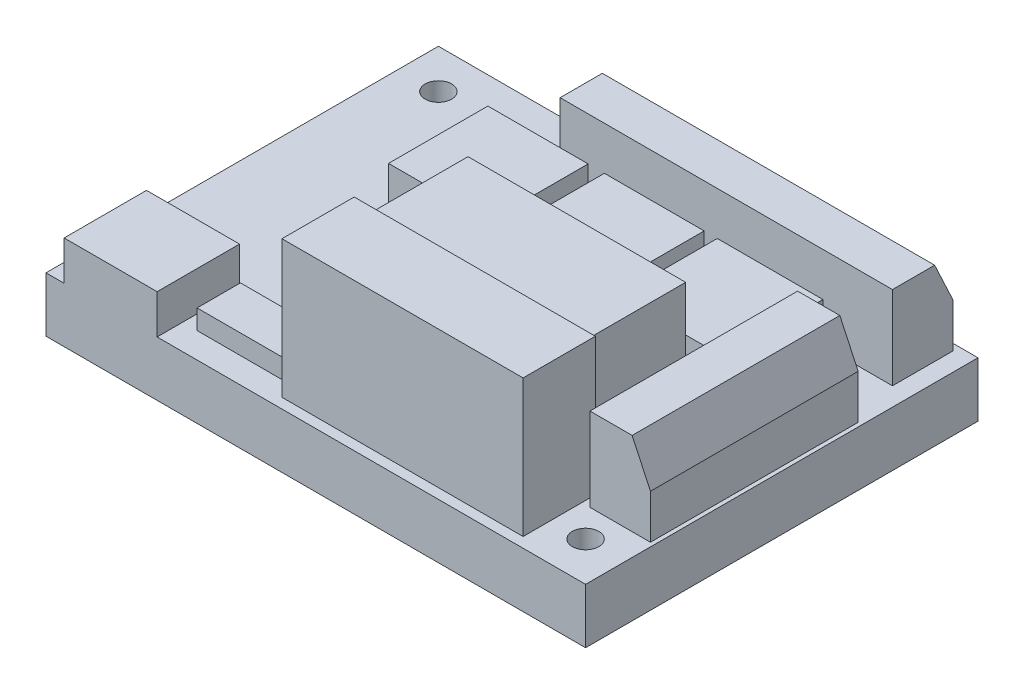
SolidWorks part; units mm, degrees
note: The reader was unsure of these and kept them because the rebuilt part matched: shared geometry of "Skizze2<3>", "Skizze2<4>", "Skizze2<5>", "Skizze2<6>", "Skizze2<7>".
ref_plane "Vorne" through (0, 0, 0) normal (0, 0, 1) x (1, 0, 0)
ref_plane "Oben" through (0, 0, 0) normal (0, 1, 0) x (1, 0, 0)
ref_plane "Rechts" through (0, 0, 0) normal (1, 0, 0) x (0, 0, -1)
sketch "Skizze1" plane through (0, 0, 0) normal (0, 1, 0) x (1, 0, 0)
  line L1 (-27.5, 20) -> (27.5, 20)
  line L2 (-27.5, 20) -> (-27.5, -20)
  line L3 (-27.5, -20) -> (27.5, -20)
  line L4 (27.5, 20) -> (27.5, -20)
  circle A0 centre (-23.5, 16) radius 1.35
  circle A1 centre (23.5, -16) radius 1.35
  dimension "D5" = 2.7
  dimension "D1" = 27.5
  dimension "D2" = 55
  dimension "D3" = 20
  dimension "D4" = 40
  dimension "D6" = 23.5
  dimension "D7" = 47
  dimension "D8" = 16
  dimension "D9" = 32
extrude "Aufsatz-Linear austragen1" add sketch "Skizze1" along normal blind 5.6
sketch "Skizze2" plane through (0, 5.6, 0) normal (0, 1, 0) x (1, 0, 0)
  line L0 (-27.5, -20) -> (27.5, -20) construction
  line L1 (-8.2565, 19.3301) -> (25.6192, 19.3301)
  line L2 (-8.2565, 19.3301) -> (-8.2565, 13.1625)
  line L3 (-8.2565, 13.1625) -> (25.6192, 13.1625)
  line L4 (25.6192, 19.3301) -> (25.6192, 13.1625)
  line L5 (20.9245, 8.1916) -> (27.0921, 8.1916)
  line L6 (20.9245, 8.1916) -> (20.9245, -12.9808)
  line L7 (20.9245, -12.9808) -> (27.0921, -12.9808)
  line L8 (27.0921, 8.1916) -> (27.0921, -12.9808)
  line L9 (-4.4823, -11.6) -> (20.096, -11.6)
  line L10 (-4.4823, -11.6) -> (-4.4823, -18.9643)
  line L11 (-4.4823, -18.9643) -> (20.096, -18.9643)
  line L12 (20.096, -11.6) -> (20.096, -18.9643)
  line L13 (-3.7459, -0.7376) -> (18.439, -0.7376)
  line L14 (-3.7459, -0.7376) -> (-3.7459, -10.3112)
  line L15 (-3.7459, -10.3112) -> (18.439, -10.3112)
  line L16 (18.439, -0.7376) -> (18.439, -10.3112)
  line L17 (-14.7003, 12.2419) -> (-4.4823, 12.2419)
  line L18 (-14.7003, 12.2419) -> (-14.7003, 2.116)
  line L19 (-14.7003, 2.116) -> (-4.4823, 2.116)
  line L20 (-4.4823, 12.2419) -> (-4.4823, 2.116)
  line L21 (-2.8254, 12.2419) -> (7.3466, 12.2419)
  line L22 (-2.8254, 12.2419) -> (-2.8254, 2.116)
  line L23 (-2.8254, 2.116) -> (7.3466, 2.116)
  line L24 (7.3466, 12.2419) -> (7.3466, 2.116)
  line L25 (8.6814, 12.2419) -> (19.4516, 12.2419)
  line L26 (8.6814, 12.2419) -> (8.6814, 2.116)
  line L27 (8.6814, 2.116) -> (19.4516, 2.116)
  line L28 (19.4516, 12.2419) -> (19.4516, 2.116)
  line L29 (-14.7003, -12.9808) -> (-5.587, -12.9808)
  line L30 (-14.7003, -12.9808) -> (-14.7003, -17.3994)
  line L31 (-14.7003, -17.3994) -> (-5.587, -17.3994)
  line L32 (-5.587, -12.9808) -> (-5.587, -17.3994)
  line L33 (-25.6547, -11.6) -> (-16.1731, -11.6)
  line L34 (-25.6547, -11.6) -> (-25.6547, -20)
  line L35 (-25.6547, -20) -> (-16.1731, -20)
  line L36 (-16.1731, -11.6) -> (-16.1731, -20)
  line L37 (68.7257, 16.3088) -> (77.2814, 16.3088) construction
  line L38 (68.7257, 8.7597) -> (73.5068, 8.7597) construction
  line L39 (68.7257, -6.9363) -> (81.4271, -6.9363) construction
  line L40 (68.7257, -14.0324) -> (82.7105, -14.0324) construction
  line L41 (68.7257, 0) -> (77.2814, 0) construction
  line M3 (-27.5, -20) -> (27.5, -20)
  dimension "D1" = 8.5557
  dimension "D2" = 12.7014
  dimension "D3" = 13.9848
  dimension "D4" = 4.7811
extrude "Aufsatz-Linear austragen2" add sketch "Skizze2" along normal blind 8.5 contours L4 L1 L2 L3 | L8 L5 L6 L7
extrude "Aufsatz-Linear austragen3" add sketch "Skizze2<3>" along normal blind 4 contours L36 L33 L34 M3
sketch "Skizze2<3>" plane through (0, 5.6, 0) normal (0, 1, 0) x (1, 0, 0) same geometry as "Skizze2"
extrude "Aufsatz-Linear austragen4" add sketch "Skizze2<4>" along normal blind 5 contours L20 L17 L18 L19 | L24 L21 L22 L23 | L28 L25 L26 L27
sketch "Skizze2<4>" plane through (0, 5.6, 0) normal (0, 1, 0) x (1, 0, 0) same geometry as "Skizze2"
extrude "Aufsatz-Linear austragen5" add sketch "Skizze2<5>" along normal blind 12.5 contours L16 L13 L14 L15
sketch "Skizze2<5>" plane through (0, 5.6, 0) normal (0, 1, 0) x (1, 0, 0) same geometry as "Skizze2"
extrude "Aufsatz-Linear austragen6" add sketch "Skizze2<6>" along normal blind 14 contours L12 L9 L10 L11
sketch "Skizze2<6>" plane through (0, 5.6, 0) normal (0, 1, 0) x (1, 0, 0) same geometry as "Skizze2"
extrude "Aufsatz-Linear austragen7" add sketch "Skizze2<7>" along normal blind 2 contours L32 L29 L30 L31
sketch "Skizze2<7>" plane through (0, 5.6, 0) normal (0, 1, 0) x (1, 0, 0) same geometry as "Skizze2"
chamfer "Fase1" distance 4 angle 25 2 edges at (27.0921, 14.1, 2.3946) (8.6814, 14.1, -19.3301)
move or copy body "Körper-Verschieben/Kopieren1" [suppressed] bodies to move or copy 109
